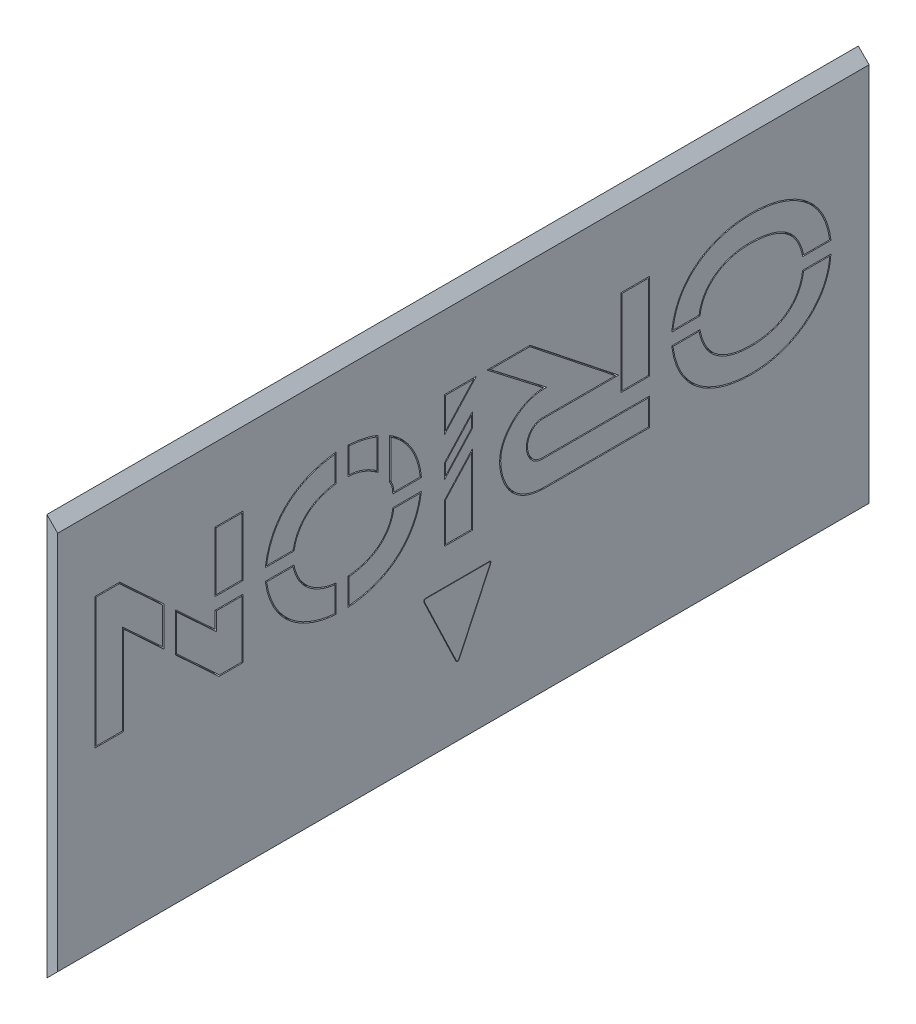
SolidWorks part; units mm, degrees
material "ABS"
ref_plane "Front Plane" through (0, 0, 0) normal (0, 0, 1) x (1, 0, 0)
ref_plane "Top Plane" through (0, 0, 0) normal (0, 1, 0) x (1, 0, 0)
ref_plane "Right Plane" through (0, 0, 0) normal (1, 0, 0) x (0, 0, -1)
sketch "Sketch1" plane through (0, 0, 0) normal (0, 0, 1) x (1, 0, 0)
  line L0 (-15, 45) -> (15, 45)
  line L1 (-15, 45) -> (15, 45) construction
  line L2 (-15, 45) -> (-15, -45) construction
  line L3 (-15, -45) -> (15, -45) construction
  line L4 (15, 45) -> (15, -45) construction
  line L5 (-15, 45) -> (15, -45) construction
  line L6 (-15, -45) -> (15, 45) construction
  line L7 (15, 45) -> (15, -45)
  line L8 (15, -45) -> (-15, -45)
  line L9 (-15, -45) -> (-15, -10.9)
  line L10 (-15, -10.9) -> (13, -10.9)
  line L11 (13, -10.9) -> (13, 30)
  line L12 (13, 30) -> (-15, 30)
  line L13 (-15, 30) -> (-15, 45)
  point P0 (0, 0)
  dimension "D1" = 90
  dimension "D2" = 30
  dimension "D3" = 40.9
  dimension "D4" = 15
  dimension "D5" = 2
extrude "Boss-Extrude1" add sketch "Sketch1" along normal blind 150
sketch "Sketch2" plane through (0, 0, 150) normal (0, 0, 1) x (1, 0, 0)
  line L0 (13, 30) -> (-7.8, 30) construction
  line L1 (-15, 30) -> (13, 30) construction
  line L2 (2.6, 30) -> (2.6, 33.89) construction
  line L3 (2.6, 33.89) -> (7.5, 33.89) construction
  line L4 (13, 30) -> (13, -10.9) construction
  line L5 (13, 9.55) -> (15, 9.55) construction
  line L7 (15, -45) -> (15, 45) construction
  circle A0 centre (7.5, 33.89) radius 2.35
  circle A1 centre (-2.3, 33.89) radius 2.35
  circle A4 centre (7.5, -14.79) radius 2.35
  circle A5 centre (-2.3, -14.79) radius 2.35
  dimension "D4" = 4.7
  dimension "D1" = 20.8
  dimension "D2" = 3.89
  dimension "D3" = 4.9
extrude "Cut-Extrude1" cut sketch "Sketch2" against normal blind 8
sketch "Sketch3" plane through (0, 0, 0) normal (0, 0, -1) x (-1, 0, 0)
  line L0 (-13, 30) -> (7.8, 30) construction
  line L1 (15, 30) -> (-13, 30) construction
  line L2 (-13, 30) -> (-13, -10.9) construction
  line L3 (-13, 9.55) -> (-15, 9.55) construction
  line L5 (-2.6, 30) -> (-2.6, 33.89) construction
  line L6 (-2.6, 33.89) -> (-7.5, 33.89) construction
  line L7 (-15, -45) -> (-15, 45) construction
  circle A0 centre (-7.5, 33.89) radius 2.35
  circle A1 centre (2.3, 33.89) radius 2.35
  circle A4 centre (-7.5, -14.79) radius 2.35
  circle A5 centre (2.3, -14.79) radius 2.35
  dimension "D4" = 4.7
  dimension "D1" = 20.8
  dimension "D2" = 3.89
  dimension "D3" = 4.9
extrude "Cut-Extrude2" cut sketch "Sketch3" against normal blind 8
chamfer "Chamfer1" distance 1 angle 45 8 edges at (5.15, 33.89, 0) (0.05, 33.89, 0) (-4.65, 33.89, 150) (9.85, 33.89, 150) (5.15, -14.79, 150) (0.05, -14.79, 150) (-4.65, -14.79, 0) (9.85, -14.79, 0)
sketch "Sketch4" plane through (0, 0, 150) normal (0, 0, 1) x (1, 0, 0)
  line L0 (0, 0) -> (15, 0) construction
  line L1 (-15, -45) -> (5.1, -45)
  line L2 (-15, -45) -> (-15, -39)
  line L3 (-15, -39) -> (5.1, -39)
  line L4 (5.1, -45) -> (5.1, -39)
  line L5 (15, -45) -> (15, 45) construction
  line L6 (-15, 39) -> (5.1, 39)
  line L7 (5.1, 45) -> (5.1, 39)
  line L8 (-15, 45) -> (5.1, 45)
  line L9 (-15, 45) -> (-15, 39)
  dimension "D1" = 6
  dimension "D2" = 20.1
extrude "Cut-Extrude3" cut sketch "Sketch4" against normal through all
chamfer "Chamfer2" distance 9.9 angle 45 2 edges at (15, -45, 75) (15, 45, 75)
sketch "Sketch5" plane through (0, 39, 0) normal (0, 1, 0) x (1, 0, 0)
  line L0 (-4.95, 0) -> (-4.95, -25) construction
  line L1 (-15, 0) -> (5.1, 0) construction
  line L2 (-4.95, -25) -> (-4.95, -50) construction
  line L3 (-4.95, -50) -> (-4.95, -75) construction
  line L4 (-4.95, -100) -> (-4.95, -125) construction
  line L5 (-4.95, -125) -> (-4.95, -150) construction
  line L6 (-15, -150) -> (5.1, -150) construction
  line L8 (-4.95, -75) -> (-4.95, -100) construction
  line L10 (5.1, 0) -> (-15, 0) construction
  line L11 (5.1, 0) -> (5.1, -150) construction
  line L12 (5.1, -150) -> (-15, -150) construction
  line L13 (-15, 0) -> (-15, -150) construction
  circle A0 centre (-4.95, -25) radius 2.35
  circle A1 centre (-4.95, -50) radius 2.35
  circle A2 centre (-4.95, -100) radius 2.35
  circle A3 centre (-4.95, -125) radius 2.35
  dimension "D1" = 4.7
  dimension "D2" = 4.7
  dimension "D3" = 4.7
  dimension "D4" = 4.7
  dimension "D5" = 20.1
  dimension "D6" = 150
extrude "Cut-Extrude4" cut sketch "Sketch5" against normal blind 8
chamfer "Chamfer3" distance 1 angle 45 4 edges at (-4.95, 39, 127.35) (-4.95, 39, 102.35) (-4.95, 39, 52.35) (-4.95, 39, 27.35)
sketch "Sketch6" plane through (0, -39, 0) normal (0, -1, 0) x (1, 0, 0)
  line L1 (5, 121) -> (-15, 121) construction
  line L2 (5, 121) -> (5, 29) construction
  line L3 (5, 29) -> (-15, 29) construction
  line L4 (-15, 121) -> (-15, 29) construction
  line L5 (-15, 0) -> (-15, 150) construction
  line L6 (5.1, 150) -> (-15, 150) construction
  line L7 (5.1, 0) -> (-15, 0) construction
  line L8 (-5, 121) -> (-5, 90.3333) construction
  line L9 (-5, 90.3333) -> (-5, 59.6667) construction
  line L10 (-5, 59.6667) -> (-5, 29) construction
  circle A0 centre (-5, 59.6667) radius 6.1
  circle A1 centre (-5, 90.3333) radius 6.1
  dimension "D3" = 12.2
  dimension "D4" = 12.2
  dimension "D1" = 29
  dimension "D2" = 29
  dimension "D5" = 10
  dimension "D6" = 10
  dimension "D7" = 20
extrude "Cut-Extrude5" cut sketch "Sketch6" against normal blind 3.2
sketch "Sketch8" plane through (-15, 0, 0) normal (-1, 0, 0) x (0, 0, 1)
  line L0 (150, -10.9) -> (130, -10.9) construction
  line L1 (150, -10.9) -> (0, -10.9) construction
  line L2 (0, -10.9) -> (20, -10.9) construction
  line L3 (150, -10.9) -> (0, -10.9) construction
  line L5 (20, -10.9) -> (130, -10.9)
  line L6 (20, -10.9) -> (20, -32.8)
  line L7 (20, -32.8) -> (130, -32.8)
  line L8 (130, -10.9) -> (130, -32.8)
  line L9 (53.5667, -35.8) -> (65.7667, -35.8) construction
  dimension "D1" = 20
  dimension "D2" = 20
  dimension "D3" = 3
extrude "Cut-Extrude7" cut sketch "Sketch8" against normal up to surface (28 mm away) up to face at (13, 9.55, 75)
fillet "Fillet1" radius 0.2 2 edges at (-5, -39, 84.2333) (-5, -39, 53.5667)
sketch "Sketch9" plane through (13, 0, 0) normal (-1, 0, 0) x (0, 0, 1)
  line L0 (150, 30) -> (0, 30) construction
  line L1 (35, 30) -> (115, 30)
  line L2 (35, 30) -> (35, -32.8)
  line L3 (35, -32.8) -> (115, -32.8)
  line L4 (115, 30) -> (115, -32.8)
  line L5 (20, -32.8) -> (130, -32.8) construction
  line L6 (20, -10.9) -> (20, -32.8) construction
  line L7 (130, -32.8) -> (130, -10.9) construction
  dimension "D1" = 15
  dimension "D2" = 15
extrude "Boss-Extrude2" add sketch "Sketch9" along normal blind 3
sketch "Sketch13" plane through (15, 0, 0) normal (1, 0, 0) x (0, 0, -1)
  line L0 (0, 40.3215) -> (200, 40.3215) construction
  dimension "D1" = 200
sketch "Sketch14" plane through (15, 0, 0) normal (1, 0, 0) x (0, 0, -1)
  line L0 (-36.4956, 10.5273) -> (-31.2721, 10.5273)
  line L5 (-36.4956, 8.3324) -> (-31.2721, 8.3324)
  line L6 (-12.2886, 10.5273) -> (-7.0661, 10.5273)
  line L18 (-12.2886, 8.3324) -> (-7.066, 8.3324)
  line L28 (-40.5888, -2.7025) -> (-40.5888, 2.3742)
  line L29 (-40.5888, 2.3742) -> (-60.4762, 2.3742)
  line L30 (-40.5888, -2.7025) -> (-60.0956, -2.7025)
  line L31 (-46.326, 8.573) -> (-62.6678, 21.5327)
  line L32 (-40.6092, 5.5469) -> (-45.849, 5.5469)
  line L33 (-40.6092, 5.5469) -> (-40.6092, 21.5327)
  line L34 (-40.6092, 21.5327) -> (-45.849, 21.5327)
  line L35 (-45.849, 5.5469) -> (-45.849, 21.5327)
  line L36 (-62.6678, 21.5327) -> (-70.6319, 21.5327)
  line L37 (-60.1854, 13.4714) -> (-70.6319, 21.5327)
  line L38 (-46.326, 8.573) -> (-60.4651, 8.573)
  line L39 (-73.2957, -2.7455) -> (-78.5231, -2.7455)
  line L40 (-78.5231, -2.7455) -> (-78.5231, 4.6129)
  line L41 (-78.5231, 4.6129) -> (-73.2957, 10.3206)
  line L42 (-73.2957, 10.3206) -> (-73.2957, -2.7455)
  line L43 (-73.2957, 13.5913) -> (-73.2957, 16.2892)
  line L44 (-73.2957, 16.2892) -> (-78.5231, 10.5816)
  line L45 (-78.5231, 10.5816) -> (-78.5231, 7.8837)
  line L46 (-78.5231, 7.8837) -> (-73.2957, 13.5913)
  line L47 (-78.5231, 21.5327) -> (-78.5231, 15.0786)
  line L48 (-78.5231, 15.0786) -> (-72.6122, 21.5327)
  line L49 (-72.6122, 21.5327) -> (-78.5231, 21.5327)
  line L50 (-70.2528, -9.306) -> (-81.921, -9.306)
  line L51 (-82.1556, -10.1317) -> (-76.4224, -22.1276)
  line L52 (-75.7591, -22.1331) -> (-70.03, -9.9399)
  line L57 (-82.7574, 8.2013) -> (-88.0471, 8.2013)
  line L58 (-96.3115, -3.6117) -> (-96.3115, 1.3953)
  line L59 (-106.3217, 8.2013) -> (-111.6297, 8.2013)
  line L60 (-98.5064, -3.6117) -> (-98.5064, 1.3953)
  line L61 (-82.7574, 10.4038) -> (-88.0471, 10.4038)
  line L62 (-88.6168, 12.5318) -> (-88.6168, 20.0476)
  line L63 (-90.8066, 15.2505) -> (-90.8066, 21.1655)
  line L64 (-96.3115, 22.3789) -> (-96.3115, 17.2957)
  line L65 (-98.5064, 17.2957) -> (-98.5064, 22.3789)
  line L66 (-106.3217, 10.4038) -> (-111.6297, 10.4038)
  line L67 (-120.1841, -2.7367) -> (-128.1991, 4.7119)
  line L68 (-115.7458, 21.5327) -> (-120.9079, 21.5327)
  line L69 (-115.7458, 21.5327) -> (-115.7458, 10.4038)
  line L70 (-115.7458, 10.4038) -> (-120.9079, 10.4038)
  line L71 (-120.9079, 21.5327) -> (-120.9079, 10.4038)
  line L72 (-115.7694, 8.2108) -> (-120.8778, 8.2108)
  line L73 (-115.7694, 8.2108) -> (-115.7694, -2.7367)
  line L74 (-115.7694, -2.7367) -> (-120.1841, -2.7367)
  line L76 (-120.8778, 8.2108) -> (-120.8778, 5.1361)
  line L77 (-120.8778, 5.1361) -> (-128.1991, 11.94)
  line L78 (-143.0831, 21.5327) -> (-138.5211, 21.5327)
  line L79 (-137.8217, -2.7367) -> (-143.0831, -2.7367)
  line L80 (-143.0831, -2.7367) -> (-143.0831, 21.5327)
  line L81 (-137.8217, -2.7367) -> (-137.8217, 13.6545)
  line L82 (-128.1991, 4.7119) -> (-128.1991, 11.94)
  line L83 (-130.3889, 6.7469) -> (-130.3889, 13.9751)
  line L84 (-130.3889, 6.7469) -> (-137.8217, 13.6545)
  line L85 (-130.3889, 13.9751) -> (-138.5211, 21.5327)
  line L86 (18.2777, -4.184) -> (18.2777, 21.6862) construction
  line L87 (33.0451, -4.184) -> (3.5103, -4.184) construction
  line L88 (33.0451, -4.184) -> (33.0451, 7.7657) construction
  line L89 (33.0451, 21.6862) -> (3.5103, 21.6862) construction
  line L90 (3.5103, -4.184) -> (3.5103, 7.7657) construction
  line L91 (33.0451, 8.7511) -> (3.5103, 8.7511) construction
  line L92 (8.7684, -4.184) -> (8.7684, 7.7657) construction
  line L93 (32.9804, 9.9603) -> (27.6851, 9.9603) construction
  line L94 (33.0022, 7.7657) -> (27.7194, 7.7657) construction
  line L95 (27.7194, 7.7657) -> (18.2777, 7.7657) construction
  line L96 (8.8359, 7.7657) -> (3.5532, 7.7657) construction
  line L97 (27.6851, 9.9603) -> (18.2777, 9.9603) construction
  line L98 (8.8703, 9.9603) -> (3.575, 9.9603) construction
  line L99 (18.2777, 9.9603) -> (8.8703, 9.9603) construction
  line L100 (18.2777, 7.7657) -> (8.8359, 7.7657) construction
  line L101 (33.0451, 8.7511) -> (33.0451, 9.9603) construction
  line L102 (33.0451, 9.9603) -> (33.0451, 21.6862) construction
  line L103 (33.0451, 7.7657) -> (33.0451, 8.7511) construction
  line L104 (8.7684, 7.7657) -> (8.7684, 8.7511) construction
  line L105 (8.7684, 9.9603) -> (8.7684, 21.6862) construction
  line L106 (8.7684, 8.7511) -> (8.7684, 9.9603) construction
  line L107 (3.5103, 8.7511) -> (3.5103, 9.9603) construction
  line L108 (3.5103, 9.9603) -> (3.5103, 21.6862) construction
  line L109 (3.5103, 7.7657) -> (3.5103, 8.7511) construction
  line L110 (3.575, 9.9603) -> (3.5103, 9.9603) construction
  line L111 (3.5532, 7.7657) -> (3.5103, 7.7657) construction
  line L112 (33.0451, 7.7657) -> (33.0022, 7.7657) construction
  line L113 (33.0451, 9.9603) -> (32.9804, 9.9603) construction
  ellipse E12 centre (18.2777, 8.7511) end of major axis (3.5103, 8.7511) minor radius 12.9351 (32.9804, 9.9603) -> (3.575, 9.9603) ccw construction
  ellipse E13 centre (18.2777, 8.7511) end of major axis (8.7684, 8.7511) minor radius 8.2835 (27.6851, 9.9603) -> (8.8703, 9.9603) ccw construction
  ellipse E14 centre (18.2777, 8.7511) end of major axis (8.7684, 8.7511) minor radius 8.2835 (27.7194, 7.7657) -> (27.787, 8.7511) ccw construction
  ellipse E15 centre (18.2777, 8.7511) end of major axis (8.7684, 8.7511) minor radius 8.2835 (27.787, 8.7511) -> (27.6851, 9.9603) ccw construction
  ellipse E16 centre (18.2777, 8.7511) end of major axis (3.5103, 8.7511) minor radius 12.9351 (33.0451, 8.7511) -> (32.9804, 9.9603) ccw construction
  ellipse E17 centre (18.2777, 8.7511) end of major axis (3.5103, 8.7511) minor radius 12.9351 (33.0022, 7.7657) -> (33.0451, 8.7511) ccw construction
  ellipse E18 centre (18.2777, 8.7511) end of major axis (8.7684, 8.7511) minor radius 8.2835 (8.7684, 8.7511) -> (8.8359, 7.7657) ccw construction
  ellipse E19 centre (18.2777, 8.7511) end of major axis (8.7684, 8.7511) minor radius 8.2835 (8.8359, 7.7657) -> (27.7194, 7.7657) ccw construction
  ellipse E20 centre (18.2777, 8.7511) end of major axis (8.7684, 8.7511) minor radius 8.2835 (8.8703, 9.9603) -> (8.7684, 8.7511) ccw construction
  ellipse E21 centre (18.2777, 8.7511) end of major axis (3.5103, 8.7511) minor radius 12.9351 (3.575, 9.9603) -> (3.5103, 8.7511) ccw construction
  ellipse E22 centre (18.2777, 8.7511) end of major axis (3.5103, 8.7511) minor radius 12.9351 (3.5532, 7.7657) -> (33.0022, 7.7657) ccw construction
  ellipse E23 centre (18.2777, 8.7511) end of major axis (3.5103, 8.7511) minor radius 12.9351 (3.5103, 8.7511) -> (3.5532, 7.7657) ccw construction
  spline S0 degree 3 poles (-82.7574, 8.2013) (-83.4912, 2.2699) (-87.8439, -3.0097) (-96.3115, -3.6117) knots 0 0 0 0 1 1 1 1
  spline S1 degree 3 poles (-60.4762, 2.3742) (-62.2068, 2.4165) (-63.1625, 4.318) (-63.178, 6.7336) (-62.1685, 8.5084) (-60.4651, 8.573) knots 0 0 0 0 0.4566 0.5566 1 1 1 1
  spline S2 degree 3 poles (-60.0956, -2.7025) (-65.2098, -2.6454) (-68.1602, 1.4096) (-68.5039, 9.5608) (-64.024, 13.4438) (-60.1854, 13.4714) knots 0 0 0 0 0.455727 0.555727 1 1 1 1
  spline S3 degree 3 poles (-88.0471, 8.2013) (-88.4531, 4.6726) (-91.1677, 1.8581) (-96.3115, 1.3953) knots 0 0 0 0 1 1 1 1
  spline S4 degree 3 poles (-98.5064, 1.3953) (-101.942, 1.7561) (-105.4701, 3.744) (-106.3217, 8.2013) knots 0 0 0 0 1 1 1 1
  spline S5 degree 3 poles (-111.6297, 8.2013) (-110.4981, 0.1832) (-104.3692, -3.2385) (-98.5064, -3.6117) knots 0 0 0 0 1 1 1 1
  spline S6 degree 3 poles (-88.0471, 10.4038) (-88.0698, 11.1486) (-88.1652, 11.8863) (-88.6168, 12.5318) knots 0 0 0 0 1 1 1 1
  spline S7 degree 3 poles (-82.7574, 10.4038) (-83.101, 14.6535) (-85.3701, 18.1067) (-88.6168, 20.0476) knots 0 0 0 0 1 1 1 1
  spline S8 degree 3 poles (-98.5064, 17.2957) (-101.9491, 16.8356) (-105.4387, 15.1234) (-106.3217, 10.4038) knots 0 0 0 0 1 1 1 1
  spline S9 degree 3 poles (-111.6297, 10.4038) (-110.5268, 18.6751) (-104.3908, 21.7132) (-98.5064, 22.3789) knots 0 0 0 0 1 1 1 1
  spline S10 degree 3 poles (-96.3115, 22.3789) (-94.3774, 22.2456) (-92.5397, 21.8915) (-90.8066, 21.1655) knots 0 0 0 0 1 1 1 1
  spline S11 degree 3 poles (-96.3115, 17.2957) (-94.354, 17.2906) (-92.5652, 16.512) (-90.8066, 15.2505) knots 0 0 0 0 1 1 1 1
  spline S12 degree 3 poles (-70.2528, -9.306) (-69.877, -9.3072) (-69.8463, -9.5532) (-70.03, -9.9399) knots 0 0 0 0 1 1 1 1
  spline S13 degree 3 poles (-81.921, -9.306) (-82.4751, -9.3153) (-82.3232, -9.7692) (-82.1556, -10.1317) knots 0 0 0 0 1 1 1 1
  spline S14 degree 3 poles (-76.4224, -22.1276) (-76.2642, -22.4624) (-75.9143, -22.4572) (-75.7591, -22.1331) knots 0 0 0 0 1 1 1 1
  spline S15 degree 3 poles (-31.2721, 10.5273) (-30.7825, 14.4952) (-26.8371, 17.5394) (-16.9674, 17.3948) (-13.1837, 15.1848) (-12.2886, 10.5273) knots 0 0 0 0 0.44939 0.54939 1 1 1 1
  spline S16 degree 3 poles (-36.4956, 10.5273) (-35.6066, 18.7825) (-21.8416, 25.6599) (-8.056, 18.9379) (-7.0661, 10.5273) knots 0 0 0 0 0.497299 1 1 1 1
  spline S17 degree 3 poles (-31.2721, 8.3324) (-30.3553, 3.2997) (-26.2388, 1.1158) (-17.2032, 1.1024) (-12.8907, 3.5838) (-12.2886, 8.3324) knots 0 0 0 0 0.434184 0.534184 1 1 1 1
  spline S18 degree 3 poles (-36.4956, 8.3324) (-35.5716, 0.7317) (-28.9356, -3.6005) (-14.091, -3.7098) (-7.4042, 1.8298) (-7.066, 8.3324) knots 0 0 0 0 0.429899 0.529899 1 1 1 1
extrude "Cut-Extrude8" cut sketch "Sketch14" against normal blind 1 contours L33 L32 L35 L34 | L29 S1 L38 L31 L36 L37 S2 L30 L28 | L42 L39 L40 L41 | L43 L44 L45 L46 | L49 L47 L48 | L50 S13 L51 S14 L52 S12 | L58 S3 L57 S0 | S7 L62 S6 L61 | S9 L65 S8 L66 | S5 L60 S4 L59 | L76 L77 L82 L67 L74 L73 L72 | L69 L68 L71 L70 | L78 L85 L83 L84 L81 L79 L80 | S11 L63 S10 L64 | S16 L6 S15 L0 | S18 L18 S17 L5
sketch "Sketch15" plane through (14, 0, 0) normal (1, 0, 0) x (0, 0, -1)
  line L0 (-143.0831, 21.5327) -> (-143.0831, -2.7367) construction
  line L1 (-143.0831, -2.7367) -> (-137.8217, -2.7367) construction
  line L2 (-137.8217, -2.7367) -> (-137.8217, 13.6545) construction
  line L3 (-137.8217, 13.6545) -> (-130.3889, 6.7469) construction
  line L4 (-130.3889, 6.7469) -> (-130.3889, 13.9751) construction
  line L5 (-130.3889, 13.9751) -> (-138.5211, 21.5327) construction
  line L6 (-138.5211, 21.5327) -> (-143.0831, 21.5327) construction
  line L7 (-120.9079, 10.4038) -> (-115.7458, 10.4038) construction
  line L8 (-115.7458, 10.4038) -> (-115.7458, 21.5327) construction
  line L9 (-115.7458, 21.5327) -> (-120.9079, 21.5327) construction
  line L10 (-120.9079, 21.5327) -> (-120.9079, 10.4038) construction
  line L11 (-115.7694, 8.2108) -> (-120.8778, 8.2108) construction
  line L12 (-120.8778, 8.2108) -> (-120.8778, 5.1361) construction
  line L13 (-120.8778, 5.1361) -> (-128.1991, 11.94) construction
  line L14 (-128.1991, 11.94) -> (-128.1991, 4.7119) construction
  line L15 (-128.1991, 4.7119) -> (-120.1841, -2.7367) construction
  line L16 (-120.1841, -2.7367) -> (-115.7694, -2.7367) construction
  line L17 (-115.7694, -2.7367) -> (-115.7694, 8.2108) construction
  line L18 (-70.2528, -9.306) -> (-81.921, -9.306) construction
  line L19 (-82.1556, -10.1317) -> (-76.4224, -22.1276) construction
  line L20 (-75.7591, -22.1331) -> (-70.03, -9.9399) construction
  line L21 (-82.7574, 8.2013) -> (-88.0471, 8.2013) construction
  line L22 (-96.3115, 1.3953) -> (-96.3115, -3.6117) construction
  line L23 (-106.3217, 8.2013) -> (-111.6297, 8.2013) construction
  line L24 (-98.5064, -3.6117) -> (-98.5064, 1.3953) construction
  line L25 (-111.6297, 10.4038) -> (-106.3217, 10.4038) construction
  line L26 (-98.5064, 17.2957) -> (-98.5064, 22.3789) construction
  line L27 (-96.3115, 22.3789) -> (-96.3115, 17.2957) construction
  line L28 (-90.8066, 15.2505) -> (-90.8066, 21.1655) construction
  line L29 (-88.0471, 10.4038) -> (-82.7574, 10.4038) construction
  line L30 (-88.6168, 20.0476) -> (-88.6168, 12.5318) construction
  line L31 (-78.5231, 15.0786) -> (-72.6122, 21.5327) construction
  line L32 (-72.6122, 21.5327) -> (-78.5231, 21.5327) construction
  line L33 (-78.5231, 21.5327) -> (-78.5231, 15.0786) construction
  line L34 (-78.5231, 7.8837) -> (-73.2957, 13.5913) construction
  line L35 (-73.2957, 13.5913) -> (-73.2957, 16.2892) construction
  line L36 (-73.2957, 16.2892) -> (-78.5231, 10.5816) construction
  line L37 (-78.5231, 10.5816) -> (-78.5231, 7.8837) construction
  line L38 (-73.2957, 10.3206) -> (-78.5231, 4.6129) construction
  line L39 (-78.5231, 4.6129) -> (-78.5231, -2.7455) construction
  line L40 (-78.5231, -2.7455) -> (-73.2957, -2.7455) construction
  line L41 (-73.2957, -2.7455) -> (-73.2957, 10.3206) construction
  line L42 (-40.5888, -2.7025) -> (-40.5888, 2.3742) construction
  line L43 (-40.5888, 2.3742) -> (-60.4762, 2.3742) construction
  line L44 (-60.4651, 8.573) -> (-46.326, 8.573) construction
  line L45 (-46.326, 8.573) -> (-62.6678, 21.5327) construction
  line L46 (-62.6678, 21.5327) -> (-70.6319, 21.5327) construction
  line L47 (-70.6319, 21.5327) -> (-60.1854, 13.4714) construction
  line L48 (-60.0956, -2.7025) -> (-40.5888, -2.7025) construction
  line L49 (-40.6092, 21.5327) -> (-45.849, 21.5327) construction
  line L50 (-45.849, 21.5327) -> (-45.849, 5.5469) construction
  line L51 (-45.849, 5.5469) -> (-40.6092, 5.5469) construction
  line L52 (-40.6092, 5.5469) -> (-40.6092, 21.5327) construction
  line L53 (-36.4956, 10.5273) -> (-31.2721, 10.5273) construction
  line L54 (-12.2886, 10.5273) -> (-7.0661, 10.5273) construction
  line L55 (-31.2721, 8.3324) -> (-36.4956, 8.3324) construction
  line L56 (-7.066, 8.3324) -> (-12.2886, 8.3324) construction
  line L57 (-143.0831, 21.5327) -> (-143.0831, -2.7367)
  line L58 (-143.0831, -2.7367) -> (-137.8217, -2.7367)
  line L59 (-137.8217, -2.7367) -> (-137.8217, 13.6545)
  line L60 (-137.8217, 13.6545) -> (-130.3889, 6.7469)
  line L61 (-130.3889, 6.7469) -> (-130.3889, 13.9751)
  line L62 (-130.3889, 13.9751) -> (-138.5211, 21.5327)
  line L63 (-138.5211, 21.5327) -> (-143.0831, 21.5327)
  line L64 (-120.9079, 10.4038) -> (-115.7458, 10.4038)
  line L65 (-115.7458, 10.4038) -> (-115.7458, 21.5327)
  line L66 (-115.7458, 21.5327) -> (-120.9079, 21.5327)
  line L67 (-120.9079, 21.5327) -> (-120.9079, 10.4038)
  line L68 (-115.7694, 8.2108) -> (-120.8778, 8.2108)
  line L69 (-120.8778, 8.2108) -> (-120.8778, 5.1361)
  line L70 (-120.8778, 5.1361) -> (-128.1991, 11.94)
  line L71 (-128.1991, 11.94) -> (-128.1991, 4.7119)
  line L72 (-128.1991, 4.7119) -> (-120.1841, -2.7367)
  line L73 (-120.1841, -2.7367) -> (-115.7694, -2.7367)
  line L74 (-115.7694, -2.7367) -> (-115.7694, 8.2108)
  line L75 (-70.2528, -9.306) -> (-81.921, -9.306)
  line L76 (-82.1556, -10.1317) -> (-76.4224, -22.1276)
  line L77 (-75.7591, -22.1331) -> (-70.03, -9.9399)
  line L78 (-82.7574, 8.2013) -> (-88.0471, 8.2013)
  line L79 (-96.3115, 1.3953) -> (-96.3115, -3.6117)
  line L80 (-106.3217, 8.2013) -> (-111.6297, 8.2013)
  line L81 (-98.5064, -3.6117) -> (-98.5064, 1.3953)
  line L82 (-111.6297, 10.4038) -> (-106.3217, 10.4038)
  line L83 (-98.5064, 17.2957) -> (-98.5064, 22.3789)
  line L84 (-96.3115, 22.3789) -> (-96.3115, 17.2957)
  line L85 (-90.8066, 15.2505) -> (-90.8066, 21.1655)
  line L86 (-88.0471, 10.4038) -> (-82.7574, 10.4038)
  line L87 (-88.6168, 20.0476) -> (-88.6168, 12.5318)
  line L88 (-78.5231, 15.0786) -> (-72.6122, 21.5327)
  line L89 (-72.6122, 21.5327) -> (-78.5231, 21.5327)
  line L90 (-78.5231, 21.5327) -> (-78.5231, 15.0786)
  line L91 (-78.5231, 7.8837) -> (-73.2957, 13.5913)
  line L92 (-73.2957, 13.5913) -> (-73.2957, 16.2892)
  line L93 (-73.2957, 16.2892) -> (-78.5231, 10.5816)
  line L94 (-78.5231, 10.5816) -> (-78.5231, 7.8837)
  line L95 (-73.2957, 10.3206) -> (-78.5231, 4.6129)
  line L96 (-78.5231, 4.6129) -> (-78.5231, -2.7455)
  line L97 (-78.5231, -2.7455) -> (-73.2957, -2.7455)
  line L98 (-73.2957, -2.7455) -> (-73.2957, 10.3206)
  line L99 (-40.5888, -2.7025) -> (-40.5888, 2.3742)
  line L100 (-40.5888, 2.3742) -> (-60.4762, 2.3742)
  line L101 (-60.4651, 8.573) -> (-46.326, 8.573)
  line L102 (-46.326, 8.573) -> (-62.6678, 21.5327)
  line L103 (-62.6678, 21.5327) -> (-70.6319, 21.5327)
  line L104 (-70.6319, 21.5327) -> (-60.1854, 13.4714)
  line L105 (-60.0956, -2.7025) -> (-40.5888, -2.7025)
  line L106 (-40.6092, 21.5327) -> (-45.849, 21.5327)
  line L107 (-45.849, 21.5327) -> (-45.849, 5.5469)
  line L108 (-45.849, 5.5469) -> (-40.6092, 5.5469)
  line L109 (-40.6092, 5.5469) -> (-40.6092, 21.5327)
  line L110 (-36.4956, 10.5273) -> (-31.2721, 10.5273)
  line L111 (-12.2886, 10.5273) -> (-7.0661, 10.5273)
  line L112 (-31.2721, 8.3324) -> (-36.4956, 8.3324)
  line L113 (-7.066, 8.3324) -> (-12.2886, 8.3324)
  line L114 (-142.8831, 21.3327) -> (-142.8831, -2.5367)
  line L115 (-142.8831, -2.5367) -> (-138.0217, -2.5367)
  line L116 (-138.0217, -2.5367) -> (-138.0217, 14.1134)
  line L117 (-138.0217, 14.1134) -> (-130.5889, 7.2058)
  line L118 (-130.5889, 7.2058) -> (-130.5889, 13.8879)
  line L119 (-130.5889, 13.8879) -> (-138.5997, 21.3327)
  line L120 (-138.5997, 21.3327) -> (-142.8831, 21.3327)
  line L121 (-120.7079, 10.6038) -> (-115.9458, 10.6038)
  line L122 (-115.9458, 10.6038) -> (-115.9458, 21.3327)
  line L123 (-115.9458, 21.3327) -> (-120.7079, 21.3327)
  line L124 (-120.7079, 21.3327) -> (-120.7079, 10.6038)
  line L125 (-115.9694, 8.0108) -> (-120.6778, 8.0108)
  line L126 (-120.6778, 8.0108) -> (-120.6778, 4.6772)
  line L127 (-120.6778, 4.6772) -> (-127.9991, 11.4811)
  line L128 (-127.9991, 11.4811) -> (-127.9991, 4.7991)
  line L129 (-127.9991, 4.7991) -> (-120.1056, -2.5367)
  line L130 (-120.1056, -2.5367) -> (-115.9694, -2.5367)
  line L131 (-115.9694, -2.5367) -> (-115.9694, 8.0108)
  line L132 (-82.9854, 8.0013) -> (-87.8707, 8.0013)
  line L133 (-96.1115, 1.2136) -> (-96.1115, -3.3959)
  line L134 (-106.4857, 8.0013) -> (-111.398, 8.0013)
  line L135 (-98.7064, -3.3972) -> (-98.7064, 1.2167)
  line L136 (-111.3998, 10.6038) -> (-106.4865, 10.6038)
  line L137 (-98.7064, 17.4697) -> (-98.7064, 22.1538)
  line L138 (-96.1115, 22.1637) -> (-96.1115, 17.4926)
  line L139 (-91.0066, 15.6347) -> (-91.0066, 21.0317)
  line L140 (-87.8549, 10.6038) -> (-82.9759, 10.6038)
  line L141 (-88.4168, 19.6887) -> (-88.4168, 12.5935)
  line L142 (-78.3231, 15.5931) -> (-73.0665, 21.3327)
  line L143 (-73.0665, 21.3327) -> (-78.3231, 21.3327)
  line L144 (-78.3231, 21.3327) -> (-78.3231, 15.5931)
  line L145 (-78.3231, 8.3982) -> (-73.4957, 13.6691)
  line L146 (-73.4957, 13.6691) -> (-73.4957, 15.7747)
  line L147 (-73.4957, 15.7747) -> (-78.3231, 10.5038)
  line L148 (-78.3231, 10.5038) -> (-78.3231, 8.3982)
  line L149 (-73.4957, 9.806) -> (-78.3231, 4.5351)
  line L150 (-78.3231, 4.5351) -> (-78.3231, -2.5455)
  line L151 (-78.3231, -2.5455) -> (-73.4957, -2.5455)
  line L152 (-73.4957, -2.5455) -> (-73.4957, 9.806)
  line L153 (-40.7888, -2.5025) -> (-40.7888, 2.1742)
  line L154 (-40.7888, 2.1742) -> (-60.4786, 2.1742)
  line L155 (-60.4689, 8.773) -> (-46.9001, 8.773)
  line L156 (-46.9001, 8.773) -> (-62.7375, 21.3327)
  line L157 (-62.7375, 21.3327) -> (-70.0454, 21.3327)
  line L158 (-70.0454, 21.3327) -> (-59.6043, 13.2756)
  line L159 (-60.0944, -2.5025) -> (-40.7888, -2.5025)
  line L160 (-40.8092, 21.3327) -> (-45.649, 21.3327)
  line L161 (-45.649, 21.3327) -> (-45.649, 5.7469)
  line L162 (-45.649, 5.7469) -> (-40.8092, 5.7469)
  line L163 (-40.8092, 5.7469) -> (-40.8092, 21.3327)
  line L164 (-36.2713, 10.7273) -> (-31.4471, 10.7273)
  line L165 (-12.1245, 10.7273) -> (-7.2926, 10.7273)
  line L166 (-31.4379, 8.1324) -> (-36.2684, 8.1324)
  line L167 (-7.2786, 8.1324) -> (-12.1139, 8.1324)
  line L168 (-70.2531, -9.406) -> (-81.9201, -9.406)
  line L169 (-82.0649, -10.0898) -> (-76.3321, -22.0847)
  line L170 (-75.8493, -22.0899) -> (-70.1204, -9.8972)
  spline S0 degree 3 poles (1476.4305, 1258.2421) (-1683.5, -1314.9396) (1553.5072, 1269.2952) (-1661.8957, -1220.1184) knots -24.624366 -24.624366 -24.624366 -24.624366 21.54023 21.54023 21.54023 21.54023 only from (-70.03, -9.9399) to (-70.2528, -9.306) construction
  spline S1 degree 3 poles (1527.7523, -1196.123) (-1683.4419, 1218.1703) (1501.7306, -1260.9691) (-1640.0606, 1243.9009) knots -12.255789 -12.255789 -12.255789 -12.255789 14.156883 14.156883 14.156883 14.156883 only from (-81.921, -9.306) to (-82.1556, -10.1317) construction
  spline S2 degree 3 poles (1881.6447, 377.8288) (-2061.7666, -228.7032) (1920.2242, -11.829) (-2065.4795, 164.7623) knots -16.7196 -16.7196 -16.7196 -16.7196 17.803611 17.803611 17.803611 17.803611 only from (-76.4224, -22.1276) to (-75.7591, -22.1331) construction
  spline S3 degree 3 poles (-958.6793, 1793.3895) (392.6706, -2012.4622) (-120.6226, 2093.9961) (-521.0586, -1933.2518) knots -6.656338 -6.656338 -6.656338 -6.656338 9.198934 9.198934 9.198934 9.198934 only from (-96.3115, -3.6117) to (-82.7574, 8.2013) construction
  spline S4 degree 3 poles (-764.8168, -1857.8633) (0.0092, 2023.2026) (327.8141, -1970.383) (-932.0776, 1810.39) knots -11.114775 -11.114775 -11.114775 -11.114775 10.106454 10.106454 10.106454 10.106454 only from (-88.0471, 8.2013) to (-96.3115, 1.3953) construction
  spline S5 degree 3 poles (1611.2594, 1015.1224) (-2064.5308, -735.5725) (1967.5326, 431.1872) (-2091.0244, -130.8683) knots -6.08824 -6.08824 -6.08824 -6.08824 8.336567 8.336567 8.336567 8.336567 only from (-111.6297, 8.2013) to (-98.5064, -3.6117) construction
  spline S6 degree 3 poles (-2082.5771, -233.2735) (1929.4895, 478.1523) (-2045.1159, -714.3423) (1653.251, 952.5515) knots -9.053307 -9.053307 -9.053307 -9.053307 8.763207 8.763207 8.763207 8.763207 only from (-98.5064, 1.3953) to (-106.3217, 8.2013) construction
  spline S7 degree 3 poles (1392.2963, -1311.3585) (-1791.9991, 1216.1005) (1692.5057, -1051.066) (-1864.1965, 955.7451) knots -7.426825 -7.426825 -7.426825 -7.426825 9.861101 9.861101 9.861101 9.861101 only from (-106.3217, 10.4038) to (-98.5064, 17.2957) construction
  spline S8 degree 3 poles (-1968.4956, 729.3089) (1824.3138, -872.0837) (-1903.922, 1103.6533) (1442.4811, -1243.8004) knots -7.182106 -7.182106 -7.182106 -7.182106 6.848215 6.848215 6.848215 6.848215 only from (-98.5064, 22.3789) to (-111.6297, 10.4038) construction
  spline S9 degree 3 poles (-905.6512, -1811.4179) (703.2243, 1917.0692) (-977.571, -1839.3281) (1060.6895, 1643.8657) knots -16.144574 -16.144574 -16.144574 -16.144574 20.847566 20.847566 20.847566 20.847566 only from (-96.3115, 17.2957) to (-90.8066, 15.2505) construction
  spline S10 degree 3 poles (-202.869, -1975.2571) (105.877, 2033.58) (-222.0155, -1985.7625) (-290.7479, 2008.039) knots -21.244565 -21.244565 -21.244565 -21.244565 26.128807 26.128807 26.128807 26.128807 only from (-90.8066, 21.1655) to (-96.3115, 22.3789) construction
  spline S11 degree 3 poles (-2005.1508, 522.6982) (1671.3612, -993.1211) (-1544.6355, 1434.4151) (924.0094, -1691.5258) knots -10.941936 -10.941936 -10.941936 -10.941936 12.7304 12.7304 12.7304 12.7304 only from (-82.7574, 10.4038) to (-88.6168, 20.0476) construction
  spline S12 degree 3 poles (-2018.5107, -511.671) (1839.5115, 597.5154) (-2012.9762, -587.6081) (1834.5898, 560.8179) knots -17.701233 -17.701233 -17.701233 -17.701233 20.189307 20.189307 20.189307 20.189307 only from (-88.6168, 12.5318) to (-88.0471, 10.4038) construction
  spline S13 degree 3 poles (484.3196, 1925.6) (7.6929, -59.1638) (-63.0965, -5.9558) (-63.2449, 17.1362) (17.7617, 65.6714) (423.1825, -1930.7855) knots -4.253095 -4.253095 -4.253095 -4.253095 0.4566 0.5566 5.306464 5.306464 5.306464 5.306464 only from (-60.4762, 2.3742) to (-60.4651, 8.573) construction
  spline S14 degree 3 poles (-1154.6739, -1655.6052) (163.0382, 40.2028) (-69.6417, 36.5388) (-66.9899, -26.3386) (74.4773, -34.5069) (855.3347, 1772.1814) knots -3.30969 -3.30969 -3.30969 -3.30969 0.444273 0.544273 4.404197 4.404197 4.404197 4.404197 only from (-60.1854, 13.4714) to (-60.0956, -2.7025) construction
  spline S15 degree 3 poles (1961.5906, -2.8043) (-7.5276, -204.4791) (-67.2587, 18.1316) (21.0958, 16.8371) (-41.1641, -120.282) (-1159.9731, -1626.6818) knots -4.095517 -4.095517 -4.095517 -4.095517 0.44939 0.54939 4.856558 4.856558 4.856558 4.856558 only from (-31.2721, 10.5273) to (-12.2886, 10.5273) construction
  spline S16 degree 3 poles (-1752.8567, -956.3504) (72.5694, -136.0732) (-21.7871, 180.1496) (-115.1836, -135.1854) (1730.6594, -916.906) knots -2.917866 -2.917866 -2.917866 -2.917866 0.502701 3.89686 3.89686 3.89686 3.89686 only from (-7.0661, 10.5273) to (-36.4956, 10.5273) construction
  spline S17 degree 3 poles (1639.5215, 1092.1704) (-71.3667, 173.8596) (-71.6568, -3.2858) (33.5824, -4.061) (11.5701, 242.0088) (-1989.8671, -185.1443) knots -2.877891 -2.877891 -2.877891 -2.877891 0.429899 0.529899 4.2115 4.2115 4.2115 4.2115 only from (-36.4956, 8.3324) to (-7.066, 8.3324) construction
  spline S18 degree 3 poles (-1684.8035, 1100.5588) (9.4889, 138.4406) (15.6756, 1.0534) (-56.3892, 1.1607) (-54.0679, 115.5194) (1267.5339, 1527.4469) knots -3.638773 -3.638773 -3.638773 -3.638773 0.465816 0.565816 4.336812 4.336812 4.336812 4.336812 only from (-12.2886, 8.3324) to (-31.2721, 8.3324) construction
  spline S19 degree 3 poles (-70.03, -9.9399) (-69.8463, -9.5532) (-69.877, -9.3072) (-70.2528, -9.306) knots 0 0 0 0 1 1 1 1
  spline S20 degree 3 poles (-81.921, -9.306) (-82.4751, -9.3153) (-82.3232, -9.7692) (-82.1556, -10.1317) knots 0 0 0 0 1 1 1 1
  spline S21 degree 3 poles (-76.4224, -22.1276) (-76.2642, -22.4624) (-75.9143, -22.4572) (-75.7591, -22.1331) knots 0 0 0 0 1 1 1 1
  spline S22 degree 3 poles (-96.3115, -3.6117) (-87.8439, -3.0097) (-83.4912, 2.2699) (-82.7574, 8.2013) knots 0 0 0 0 1 1 1 1
  spline S23 degree 3 poles (-88.0471, 8.2013) (-88.4531, 4.6726) (-91.1677, 1.8581) (-96.3115, 1.3953) knots 0 0 0 0 1 1 1 1
  spline S24 degree 3 poles (-111.6297, 8.2013) (-110.4981, 0.1832) (-104.3692, -3.2385) (-98.5064, -3.6117) knots 0 0 0 0 1 1 1 1
  spline S25 degree 3 poles (-98.5064, 1.3953) (-101.942, 1.7561) (-105.4701, 3.744) (-106.3217, 8.2013) knots 0 0 0 0 1 1 1 1
  spline S26 degree 3 poles (-106.3217, 10.4038) (-105.4387, 15.1234) (-101.9491, 16.8356) (-98.5064, 17.2957) knots 0 0 0 0 1 1 1 1
  spline S27 degree 3 poles (-98.5064, 22.3789) (-104.3908, 21.7132) (-110.5268, 18.6751) (-111.6297, 10.4038) knots 0 0 0 0 1 1 1 1
  spline S28 degree 3 poles (-96.3115, 17.2957) (-94.354, 17.2906) (-92.5652, 16.512) (-90.8066, 15.2505) knots 0 0 0 0 1 1 1 1
  spline S29 degree 3 poles (-90.8066, 21.1655) (-92.5397, 21.8915) (-94.3774, 22.2456) (-96.3115, 22.3789) knots 0 0 0 0 1 1 1 1
  spline S30 degree 3 poles (-82.7574, 10.4038) (-83.101, 14.6535) (-85.3701, 18.1067) (-88.6168, 20.0476) knots 0 0 0 0 1 1 1 1
  spline S31 degree 3 poles (-88.6168, 12.5318) (-88.1652, 11.8863) (-88.0698, 11.1486) (-88.0471, 10.4038) knots 0 0 0 0 1 1 1 1
  spline S32 degree 3 poles (-60.4762, 2.3742) (-62.2068, 2.4165) (-63.1625, 4.318) (-63.178, 6.7336) (-62.1685, 8.5084) (-60.4651, 8.573) knots 0 0 0 0 0.4566 0.5566 1 1 1 1
  spline S33 degree 3 poles (-60.1854, 13.4714) (-64.024, 13.4438) (-68.5039, 9.5608) (-68.1602, 1.4096) (-65.2098, -2.6454) (-60.0956, -2.7025) knots 0 0 0 0 0.444273 0.544273 1 1 1 1
  spline S34 degree 3 poles (-31.2721, 10.5273) (-30.7825, 14.4952) (-26.8371, 17.5394) (-16.9674, 17.3948) (-13.1837, 15.1848) (-12.2886, 10.5273) knots 0 0 0 0 0.44939 0.54939 1 1 1 1
  spline S35 degree 3 poles (-7.0661, 10.5273) (-8.056, 18.9379) (-21.8416, 25.6599) (-35.6066, 18.7825) (-36.4956, 10.5273) knots 0 0 0 0 0.502701 1 1 1 1
  spline S36 degree 3 poles (-36.4956, 8.3324) (-35.5716, 0.7317) (-28.9356, -3.6005) (-14.091, -3.7098) (-7.4042, 1.8298) (-7.066, 8.3324) knots 0 0 0 0 0.429899 0.529899 1 1 1 1
  spline S37 degree 3 poles (-12.2886, 8.3324) (-12.8907, 3.5838) (-17.2032, 1.1024) (-26.2388, 1.1158) (-30.3553, 3.2997) (-31.2721, 8.3324) knots 0 0 0 0 0.465816 0.565816 1 1 1 1
  spline S38 degree 1 poles (-87.8707, 8.0013) (-96.1115, 1.2136) knots 0 0 1 1 construction
  spline S39 degree 1 poles (-96.1115, -3.3959) (-82.9854, 8.0013) knots 0 0 1 1 construction
  spline S40 degree 3 poles (-87.8707, 8.0013) (-87.9882, 7.1468) (-88.5127, 5.4573) (-89.8754, 3.7339) (-91.3934, 2.6304) (-92.7423, 1.9643) (-94.0458, 1.556) (-95.1865, 1.327) (-95.8062, 1.2447) (-96.1115, 1.2136) knots 0.016376 0.016376 0.016376 0.016376 0.259353 0.502331 0.62382 0.745309 0.866798 0.927542 0.988287 0.988287 0.988287 0.988287
  spline S41 degree 3 poles (-96.1115, -3.3959) (-95.6163, -3.3557) (-94.6098, -3.2371) (-92.7692, -2.8741) (-90.6798, -2.1894) (-88.5377, -1.0466) (-86.1454, 0.8494) (-84.0126, 3.7994) (-83.183, 6.5884) (-82.9854, 8.0013) knots 0.008546 0.008546 0.008546 0.008546 0.069711 0.130876 0.253206 0.375536 0.497866 0.742526 0.987186 0.987186 0.987186 0.987186
  spline S42 degree 1 poles (-111.398, 8.0013) (-98.7064, -3.3972) knots 0 0 1 1 construction
  spline S43 degree 1 poles (-98.7064, 1.2167) (-106.4857, 8.0013) knots 0 0 1 1 construction
  spline S44 degree 3 poles (-111.398, 8.0013) (-111.3259, 7.5358) (-111.1381, 6.5922) (-110.634, 4.8889) (-109.7649, 2.9892) (-108.4013, 1.0902) (-106.2293, -0.9723) (-102.978, -2.7101) (-100.1371, -3.288) (-98.7064, -3.3972) knots 0.00964 0.00964 0.00964 0.00964 0.070773 0.131906 0.254172 0.376438 0.498704 0.743237 0.987769 0.987769 0.987769 0.987769
  spline S45 degree 3 poles (-98.7064, 1.2167) (-99.5648, 1.3207) (-101.2576, 1.7219) (-103.2148, 2.784) (-104.5449, 4.0082) (-105.3951, 5.1214) (-105.9543, 6.2212) (-106.2951, 7.1994) (-106.4304, 7.7354) (-106.4857, 8.0013) knots 0.017064 0.017064 0.017064 0.017064 0.259801 0.502538 0.623906 0.745275 0.866643 0.927327 0.988012 0.988012 0.988012 0.988012
  spline S46 degree 1 poles (-106.4865, 10.6038) (-98.7064, 17.4697) knots 0 0 1 1 construction
  spline S47 degree 1 poles (-98.7064, 22.1538) (-111.3998, 10.6038) knots 0 0 1 1 construction
  spline S48 degree 3 poles (-106.4865, 10.6038) (-106.4299, 10.8834) (-106.2914, 11.4491) (-105.9469, 12.4664) (-105.385, 13.595) (-104.534, 14.7148) (-103.2044, 15.924) (-101.2531, 16.9452) (-99.5612, 17.3451) (-98.7064, 17.4697) knots 0.011404 0.011404 0.011404 0.011404 0.072156 0.132908 0.254411 0.375915 0.497418 0.740425 0.983432 0.983432 0.983432 0.983432
  spline S49 degree 3 poles (-98.7064, 22.1538) (-100.1446, 21.9765) (-103.0014, 21.341) (-106.2565, 19.6311) (-108.4255, 17.5959) (-109.7841, 15.7057) (-110.6474, 13.7895) (-111.1452, 12.0542) (-111.3299, 11.082) (-111.3998, 10.6038) knots 0.01271 0.01271 0.01271 0.01271 0.257212 0.501714 0.623965 0.746217 0.868468 0.929593 0.990719 0.990719 0.990719 0.990719
  spline S50 degree 1 poles (-96.1115, 17.4926) (-91.0066, 15.6347) knots 0 0 1 1 construction
  spline S51 degree 1 poles (-91.0066, 21.0317) (-96.1115, 22.1637) knots 0 0 1 1 construction
  spline S52 degree 3 poles (-96.1115, 17.4926) (-95.6633, 17.4797) (-94.7658, 17.3727) (-93.4782, 16.9907) (-92.2316, 16.4162) (-91.402, 15.9046) (-91.0066, 15.6347) knots 0.03317 0.03317 0.03317 0.03317 0.260074 0.486977 0.71388 0.940784 0.940784 0.940784 0.940784
  spline S53 degree 3 poles (-91.0066, 21.0317) (-91.4074, 21.1951) (-92.225, 21.4837) (-93.4838, 21.8072) (-94.7753, 22.0342) (-95.6674, 22.1291) (-96.1115, 22.1637) knots 0.023916 0.023916 0.023916 0.023916 0.258634 0.493352 0.72807 0.962788 0.962788 0.962788 0.962788
  spline S54 degree 1 poles (-82.9759, 10.6038) (-88.4168, 19.6887) knots 0 0 1 1 construction
  spline S55 degree 1 poles (-88.4168, 12.5935) (-87.8549, 10.6038) knots 0 0 1 1 construction
  spline S56 degree 3 poles (-82.9759, 10.6038) (-83.0231, 11.0898) (-83.1734, 12.0681) (-83.6706, 13.8934) (-84.644, 15.98) (-86.296, 18.0945) (-87.6746, 19.2138) (-88.4168, 19.6887) knots 0.017259 0.017259 0.017259 0.017259 0.136113 0.254967 0.492674 0.730382 0.968089 0.968089 0.968089 0.968089
  spline S57 degree 3 poles (-88.4168, 12.5935) (-88.3161, 12.4427) (-88.1416, 12.1157) (-87.9811, 11.62) (-87.89, 11.1118) (-87.8634, 10.7736) (-87.8549, 10.6038) knots 0.025323 0.025323 0.025323 0.025323 0.247708 0.470093 0.692477 0.914862 0.914862 0.914862 0.914862
  spline S58 degree 1 poles (-60.4786, 2.1742) (-60.4689, 8.773) knots 0 0 1 1 construction
  spline S59 degree 1 poles (-59.6043, 13.2756) (-60.0944, -2.5025) knots 0 0 1 1 construction
  spline S60 degree 3 poles (-60.4786, 2.1742) (-60.7174, 2.18) (-61.2115, 2.2532) (-62.0076, 2.607) (-62.7486, 3.3469) (-63.2401, 4.454) (-63.4144, 5.4918) (-63.2721, 6.5099) (-62.7734, 7.6007) (-62.0175, 8.3311) (-61.2096, 8.6858) (-60.7106, 8.7638) (-60.4689, 8.773) knots -0.000215 -0.000215 -0.000215 -0.000215 0.062319 0.124853 0.249921 0.374989 0.500057 0.625125 0.750193 0.87526 0.937794 1.000328 1.000328 1.000328 1.000328
  spline S61 degree 3 poles (-59.6043, 13.2756) (-59.8779, 13.2736) (-60.431, 13.2805) (-61.4898, 13.174) (-63.317, 12.6805) (-65.6623, 11.2196) (-67.31, 9.0767) (-68.0061, 7.1599) (-68.1563, 5.6697) (-67.9977, 4.15) (-67.63, 2.6735) (-67.0322, 1.2932) (-66.1952, 0.0554) (-65.1049, -0.9944) (-63.7481, -1.8122) (-62.3722, -2.2624) (-61.1307, -2.459) (-60.4341, -2.4987) (-60.0944, -2.5025) knots -0.022365 -0.022365 -0.022365 -0.022365 0.009583 0.04153 0.105426 0.233218 0.361009 0.424905 0.488801 0.552696 0.616592 0.680488 0.744383 0.808279 0.872175 0.936071 0.968019 0.999966 0.999966 0.999966 0.999966
  spline S62 degree 1 poles (-31.4471, 10.7273) (-12.1245, 10.7273) knots 0 0 1 1 construction
  spline S63 degree 1 poles (-7.2926, 10.7273) (-36.2713, 10.7273) knots 0 0 1 1 construction
  spline S64 degree 3 poles (-31.4471, 10.7273) (-31.3696, 11.2621) (-31.1004, 12.338) (-30.1858, 14.1849) (-28.3898, 16.0316) (-25.9288, 17.1541) (-23.6776, 17.5932) (-21.8676, 17.6784) (-20.0757, 17.5643) (-17.8644, 17.1952) (-15.9274, 16.4392) (-14.3478, 15.2005) (-13.365, 14.0114) (-12.7304, 12.7843) (-12.3442, 11.6655) (-12.1883, 11.0371) (-12.1245, 10.7273) knots 0.006503 0.006503 0.006503 0.006503 0.068273 0.130042 0.253581 0.37712 0.438889 0.500659 0.562428 0.624198 0.747737 0.809506 0.871276 0.933045 0.96393 0.994815 0.994815 0.994815 0.994815
  spline S65 degree 3 poles (-7.2926, 10.7273) (-7.3573, 11.2181) (-7.5376, 12.2145) (-8.0557, 14.0015) (-8.9931, 15.98) (-10.5113, 17.9302) (-12.978, 20.0069) (-16.7339, 21.6606) (-21.7969, 22.267) (-26.8707, 21.6321) (-30.6369, 19.9663) (-33.1032, 17.8895) (-34.6145, 15.9453) (-35.539, 13.9775) (-36.0415, 12.2028) (-36.2119, 11.2142) (-36.2713, 10.7273) knots 0.00453 0.00453 0.00453 0.00453 0.035497 0.066464 0.128398 0.190332 0.252266 0.376134 0.500001 0.623869 0.747737 0.809671 0.871605 0.933539 0.964506 0.995473 0.995473 0.995473 0.995473
  spline S66 degree 1 poles (-36.2684, 8.1324) (-7.2786, 8.1324) knots 0 0 1 1 construction
  spline S67 degree 1 poles (-12.1139, 8.1324) (-31.4379, 8.1324) knots 0 0 1 1 construction
  spline S68 degree 3 poles (-36.2684, 8.1324) (-36.1986, 7.6144) (-36.0058, 6.5615) (-35.4591, 4.6844) (-34.476, 2.6196) (-32.887, 0.6074) (-30.9486, -0.9777) (-28.7218, -2.1559) (-26.2694, -2.9491) (-23.6548, -3.3779) (-20.0462, -3.4899) (-15.7306, -2.6564) (-12.124, -0.6362) (-9.8645, 1.5766) (-8.5374, 3.5089) (-7.7802, 5.3291) (-7.4102, 6.8917) (-7.3074, 7.7207) (-7.2786, 8.1324) knots 0.004297 0.004297 0.004297 0.004297 0.035251 0.066205 0.128113 0.190022 0.25193 0.313838 0.375746 0.437654 0.499562 0.623378 0.747195 0.809103 0.871011 0.932919 0.963873 0.994827 0.994827 0.994827 0.994827
  spline S69 degree 3 poles (-12.1139, 8.1324) (-12.1581, 7.8246) (-12.2775, 7.2006) (-12.6117, 6.0776) (-13.2091, 4.831) (-14.1749, 3.6012) (-15.7462, 2.2938) (-18.1388, 1.2521) (-21.438, 0.8189) (-24.8038, 1.0738) (-27.3072, 1.9677) (-29.0032, 3.2439) (-30.0775, 4.5073) (-30.778, 5.8447) (-31.2015, 7.082) (-31.3703, 7.7862) (-31.4379, 8.1324) knots 0.005648 0.005648 0.005648 0.005648 0.036575 0.067503 0.129357 0.191211 0.253066 0.376774 0.500483 0.624192 0.747901 0.809755 0.871609 0.933464 0.964391 0.995318 0.995318 0.995318 0.995318
  spline S70 degree 1 poles (-70.1204, -9.8972) (-70.2531, -9.406) knots 0 0 1 1 construction
  spline S71 degree 1 poles (-81.9201, -9.406) (-82.0649, -10.0898) knots 0 0 1 1 construction
  spline S72 degree 1 poles (-76.3321, -22.0847) (-75.8493, -22.0899) knots 0 0 1 1 construction
  spline S73 degree 3 poles (-70.1204, -9.8972) (-70.0837, -9.82) (-70.0129, -9.6336) (-70.0222, -9.4913) (-70.0574, -9.447) (-70.1384, -9.4131) (-70.218, -9.4061) (-70.2531, -9.406) knots -0.000165 -0.000165 -0.000165 -0.000165 0.249876 0.499918 0.749959 0.874979 1 1 1 1
  spline S74 degree 3 poles (-81.9201, -9.406) (-81.9704, -9.4069) (-82.0874, -9.4223) (-82.1801, -9.4782) (-82.2245, -9.5707) (-82.1857, -9.8156) (-82.1053, -10.0023) (-82.0649, -10.0898) knots 0.000546 0.000546 0.000546 0.000546 0.125478 0.25041 0.500273 0.750137 1 1 1 1
  spline S75 degree 3 poles (-76.3321, -22.0847) (-76.3051, -22.1419) (-76.2128, -22.2586) (-76.0898, -22.287) (-75.9661, -22.258) (-75.8759, -22.1455) (-75.8493, -22.0899) knots -0.000189 -0.000189 -0.000189 -0.000189 0.249858 0.499905 0.749953 1 1 1 1
  dimension "D1" = 0.2
  dimension "D2" = 0.1
extrude "Boss-Extrude3" add sketch "Sketch15" along normal blind 1 contours L164 S64 L165 S65 | L166 S68 L167 S69 | L160 L161 L162 L163 | L153 L154 S60 L155 L156 L157 L158 S61 L159 | L149 L150 L151 L152 | L145 L146 L147 L148 | L142 L143 L144 | L140 S56 L141 S57 | L132 S40 L133 S41 | L136 S48 L137 S49 | L138 S52 L139 S53 | L134 S44 L135 S45 | L121 L122 L123 L124 | L125 L126 L127 L128 L129 L130 L131 | L114 L115 L116 L117 L118 L119 L120 | L168 S74 L169 S75 L170 S73
sketch "Sketch16" plane through (0, 0, 150) normal (0, 0, 1) x (1, 0, 0)
  line L1 (13, 47.4015) -> (-21.3814, 47.4015)
  line L2 (13, 47.4015) -> (13, -50.8178)
  line L3 (13, -50.8178) -> (-21.3814, -50.8178)
  line L4 (-21.3814, 47.4015) -> (-21.3814, -50.8178)
extrude "Cut-Extrude9" cut sketch "Sketch16" against normal through all
